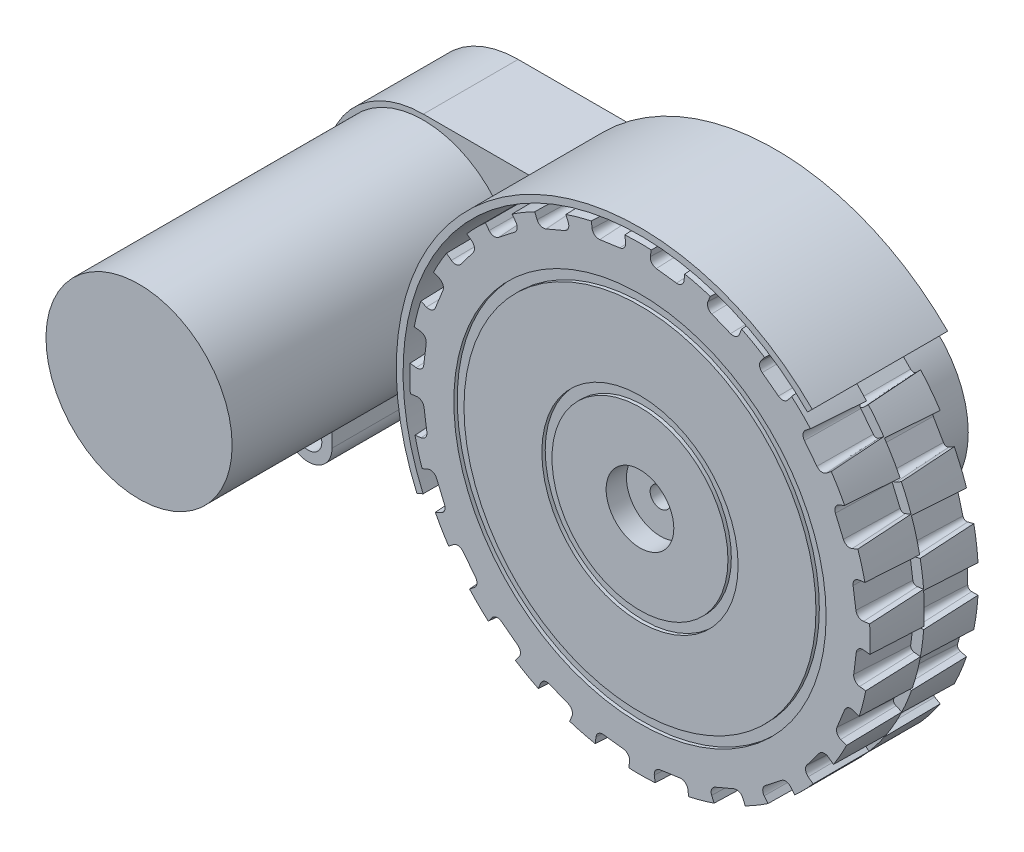
SolidWorks part; units mm, degrees
ref_plane "前视基准面" through (0, 0, 0) normal (0, 0, 1) x (1, 0, 0)
ref_plane "上视基准面" through (0, 0, 0) normal (0, 1, 0) x (1, 0, 0)
ref_plane "右视基准面" through (0, 0, 0) normal (1, 0, 0) x (0, 0, -1)
sketch "草图1" plane through (0, 0, 0) normal (0, 0, 1) x (1, 0, 0)
  circle A0 centre (0, 0) radius 34
  circle A1 centre (0, 0) radius 1.5
  dimension "D1" = 68
  dimension "D2" = 3
extrude "凸台-拉伸1" add sketch "草图1" along normal blind 8
sketch "草图2" plane through (0, 0, 8) normal (0, 0, 1) x (1, 0, 0)
  line L0 (0, 36.7804) -> (0, -36.1417) construction
  line L2 (-2.5, 34.6196) -> (2.5, 34.6196)
  line L3 (-2.5, 34.6196) -> (-2.5, 33)
  line L4 (-1.5, 32) -> (1.5, 32)
  line L5 (2.5, 34.6196) -> (2.5, 33)
  circle A0 centre (0, 0) radius 34 construction
  arc A1 (1.5, 32) -> (2.5, 33) centre (1.5, 33) ccw
  arc A2 (-2.5, 33) -> (-1.5, 32) centre (-1.5, 33) ccw
  point P11 (2.5, 32)
  point P14 (-2.5, 32)
  dimension "D4" = 1
  dimension "D1" = 5
  dimension "D2" = 2.5
  dimension "D3" = 32
extrude "切除-拉伸1" cut sketch "草图2" against normal through all draft 3
pattern_circular "阵列(圆周)1" count 24 over 360 about axis through (0, 0, 8) along (0, 0, 1) of "切除-拉伸1"
move or copy body "实体-移动/复制1" bodies to move or copy 108 copy yes number of copies 1 translate (0, 0, 8)
move or copy body "实体-移动/复制2" bodies to move or copy 110 copy no rotation origin (0, 0, 0) rotation axis (0, 0, 1) rotation angle 8
sketch "草图3" plane through (0, 0, 16) normal (0, 0, 1) x (1, 0, 0)
  circle A0 centre (0, 0) radius 5
  dimension "D1" = 10
extrude "切除-拉伸2" cut sketch "草图3" against normal blind 3
sketch "草图4" plane through (0, 0, 16) normal (0, 0, 1) x (1, 0, 0)
  circle A0 centre (0, 0) radius 13
  circle A1 centre (0, 0) radius 14.5
  circle A2 centre (0, 0) radius 27.5
  circle A3 centre (0, 0) radius 26
  dimension "D1" = 29
  dimension "D2" = 55
  dimension "D3" = 1.5
extrude "切除-拉伸3" cut sketch "草图4" against normal blind 0.5 contours A1 A0 | A2 A3 region at (-14.0899, 0, 16) region at (-26.7222, 0, 16)
sketch "草图5" plane through (0, 0, 0) normal (0, 0, -1) x (-1, 0, 0)
  circle A0 centre (0, 0) radius 26.5
  dimension "D1" = 53
extrude "切除-拉伸4" cut sketch "草图5" against normal blind 10
sketch "草图6" plane through (0, 0, 10) normal (0, 0, -1) x (-1, 0, 0)
  circle A0 centre (0, 0) radius 23
  dimension "D1" = 46
extrude "凸台-拉伸2" add sketch "草图6" along normal blind 13
sketch "草图7" plane through (0, 0, -3) normal (0, 0, -1) x (-1, 0, 0)
  circle A2 centre (0, 0) radius 23
  circle A3 centre (0, 0) radius 23
  dimension "D1" = 0
extrude "凸台-拉伸3" add sketch "草图7" along normal blind 1 draft 60
sketch "草图8" plane through (0, 0, -4) normal (0, 0, -1) x (-1, 0, 0)
  line L0 (-15.0387, 15.0387) -> (-25.4558, 25.4558)
  line L1 (15.5588, -14.5) -> (-15.0387, 15.0387)
  line L2 (0, 42.7879) -> (0, -11.5413) construction
  line L3 (15.5588, -14.5) -> (32.9507, -14.5)
  arc A0 (32.9507, -14.5) -> (-25.4558, 25.4558) centre (0, 0) ccw
  dimension "D1" = 72
  dimension "D3" = 14.5
  dimension "D4" = 45
extrude "凸台-拉伸4" add sketch "草图8" against normal blind 2
sketch "草图9" plane through (0, 0, -2) normal (0, 0, 1) x (1, 0, 0)
  line L0 (24.7487, 24.7487) -> (25.4558, 25.4558)
  line L1 (-32.9507, -14.5) -> (-32.0354, -14.0972)
  arc A0 (25.4558, 25.4558) -> (-32.9507, -14.5) centre (0, 0) ccw construction
  arc A1 (25.4558, 25.4558) -> (-32.9507, -14.5) centre (0, 0) ccw
  arc A2 (24.7487, 24.7487) -> (-32.0354, -14.0972) centre (0, 0) ccw
  dimension "D1" = 1
extrude "凸台-拉伸5" add sketch "草图9" along normal up to surface (18 mm away)
sketch "草图10" plane through (0, 0, -4) normal (0, 0, -1) x (-1, 0, 0)
  line L1 (0, 14.5) -> (52, 14.5)
  line L3 (0, -14.5) -> (52, -14.5)
  arc A0 (0, 14.5) -> (0, -14.5) centre (0, 0) ccw
  arc A1 (52, -14.5) -> (52, 14.5) centre (52, 0) ccw
  dimension "D1" = 29
  dimension "D2" = 14.5
  dimension "D3" = 52
extrude "凸台-拉伸6" add sketch "草图10" along normal blind 14
sketch "草图11" plane through (0, 0, -4) normal (0, 0, 1) x (1, 0, 0)
  circle A0 centre (-52, 0) radius 13.75
  dimension "D1" = 27.5
extrude "凸台-拉伸7" add sketch "草图11" along normal blind 42
sketch "草图12" plane through (0, 0, -18) normal (0, 0, -1) x (-1, 0, 0)
  line L0 (49.5, -19) -> (49.5, -13.4164)
  line L1 (49.5, -13.4164) -> (57.5, -13.4164)
  line L2 (57.5, -13.4164) -> (56.4224, -19.7331)
  circle A0 centre (53, -19) radius 2
  arc A1 (0, 14.5) -> (0, -14.5) centre (0, 0) ccw construction
  arc A2 (49.5, -19) -> (56.4718, -19.443) centre (53, -19) ccw
  arc A3 (52, -14.5) -> (52, 14.5) centre (52, 0) ccw construction
  line M2 (0, -14.5) -> (52, -14.5)
  arc M3 (52, -14.5) -> (52, 14.5) centre (52, 0) ccw
  dimension "D1" = 4
  dimension "D2" = 53
  dimension "D3" = 19
  dimension "D4" = 7
  dimension "D5" = 8
extrude "凸台-拉伸8" add sketch "草图12" against normal blind 25 from offset 5 contours L1 L0 M2 M3 | L0 A2 L2 A0 M3 M2 region at (-49.621, -16.75, -18) region at (-52.7321, -13.8944, -18) offset against normal yes
